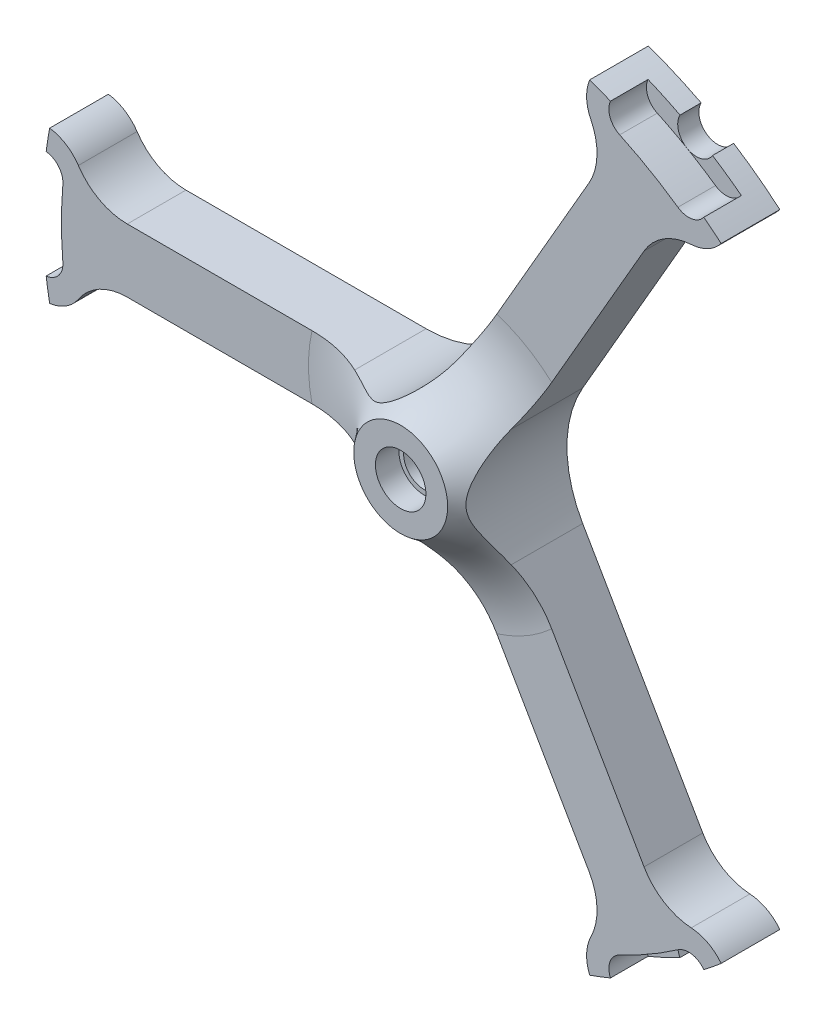
SolidWorks part; units mm, degrees
ref_plane "Plan de face" through (0, 0, 0) normal (0, 0, 1) x (1, 0, 0)
ref_plane "Plan de dessus" through (0, 0, 0) normal (0, 1, 0) x (1, 0, 0)
ref_plane "Plan de droite" through (0, 0, 0) normal (1, 0, 0) x (0, 0, -1)
sketch "Esquisse1" plane through (0, 0, 0) normal (0, 0, 1) x (1, 0, 0)
  line L19 (-1000, 0) -> (49000, 0) construction
  line L21 (-27.7888, 2.7) -> (-7.3323, 2.7)
  line L23 (-27.7888, -2.7) -> (-7.3323, -2.7)
  line L33 (16.2327, 22.7158) -> (6.0044, 5)
  line L34 (11.5561, 25.4158) -> (1.3279, 7.7)
  line L35 (11.5561, -25.4158) -> (1.3279, -7.7)
  line L36 (16.2327, -22.7158) -> (6.0044, -5)
  arc A0 (-34.3972, 6.4678) -> (-34.6976, 4.5906) centre (0, 0) ccw
  arc A7 (-33.2771, 2.8629) -> (-34.6976, 4.5906) centre (-34.8712, 3) ccw
  arc A8 (-33.2771, -2.8629) -> (-34.6976, -4.5906) centre (-34.8712, -3) cw
  arc A12 (-33.2771, 2.8629) -> (-33.2771, -2.8629) centre (0, 0) ccw
  arc A13 (-31.9549, 4.9353) -> (-34.3972, 6.4678) centre (-34.8712, 3) ccw
  arc A14 (-31.9549, -4.9353) -> (-34.3972, -6.4678) centre (-34.8712, -3) cw
  arc A15 (-34.6976, -4.5906) -> (-34.3972, -6.4678) centre (0, 0) ccw
  arc A16 (-27.7888, -2.7) -> (-31.9549, -4.9353) centre (-27.7888, -7.7) ccw
  arc A17 (-27.7888, 2.7) -> (-31.9549, 4.9353) centre (-27.7888, 7.7) cw
  arc A48 (22.7998, 26.555) -> (21.3244, 27.7538) centre (0, 0) ccw
  arc A49 (19.1178, 27.3874) -> (21.3244, 27.7538) centre (20.0337, 28.6993) ccw
  arc A50 (14.1592, 30.2502) -> (13.3733, 32.3443) centre (14.8375, 31.6993) cw
  arc A51 (19.1178, 27.3874) -> (14.1592, 30.2502) centre (0, 0) ccw
  arc A52 (20.2516, 25.2061) -> (22.7998, 26.555) centre (20.0337, 28.6993) ccw
  arc A53 (11.7034, 30.1414) -> (11.5974, 33.0227) centre (14.8375, 31.6993) cw
  arc A54 (13.3733, 32.3443) -> (11.5974, 33.0227) centre (0, 0) ccw
  arc A55 (11.5561, 25.4158) -> (11.7034, 30.1414) centre (7.226, 27.9158) ccw
  arc A56 (16.2327, 22.7158) -> (20.2516, 25.2061) centre (20.5628, 20.2158) cw
  arc A57 (11.5974, -33.0227) -> (13.3733, -32.3443) centre (0, 0) ccw
  arc A58 (14.1592, -30.2502) -> (13.3733, -32.3443) centre (14.8375, -31.6993) ccw
  arc A59 (19.1178, -27.3874) -> (21.3244, -27.7538) centre (20.0337, -28.6993) cw
  arc A60 (14.1592, -30.2502) -> (19.1178, -27.3874) centre (0, 0) ccw
  arc A61 (11.7034, -30.1414) -> (11.5974, -33.0227) centre (14.8375, -31.6993) ccw
  arc A62 (20.2516, -25.2061) -> (22.7998, -26.555) centre (20.0337, -28.6993) cw
  arc A63 (21.3244, -27.7538) -> (22.7998, -26.555) centre (0, 0) ccw
  arc A64 (16.2327, -22.7158) -> (20.2516, -25.2061) centre (20.5628, -20.2158) ccw
  arc A65 (11.5561, -25.4158) -> (11.7034, -30.1414) centre (7.226, -27.9158) cw
  arc A66 (-7.3323, -2.7) -> (1.3279, -7.7) centre (-7.3323, -12.7) cw
  arc A67 (6.0044, -5) -> (6.0044, 5) centre (14.6647, 0) cw
  arc A68 (1.3279, 7.7) -> (-7.3323, 2.7) centre (-7.3323, 12.7) cw
  point P38 (0, 0)
  point P50 (3.1177, 0)
  point P55 (0, 0)
  point P56 (0, 0)
  point P80 (0, 0)
  dimension "D1" = 70
  dimension "D3" = 3
  dimension "D2" = 3.2
  dimension "D4" = 5
  dimension "D5" = 10
extrude "Boss.-Extru.1" add sketch "Esquisse1" along normal blind 5
sketch "Esquisse7" plane through (0, 0, 0) normal (0, 0, -1) x (-1, 0, 0)
  line L0 (-1000, 0) -> (49000, 0) construction
  arc A0 (34.6976, -4.5906) -> (34.6976, 4.5906) centre (0, 0) ccw
  arc A2 (33.2771, -2.8629) -> (33.2771, 2.8629) centre (0, 0) ccw
  arc A4 (34.9634, 1.5996) -> (34.9634, -1.5996) centre (35, 0) ccw
  arc A5 (34.6976, 4.5906) -> (33.2771, 2.8629) centre (34.8712, 3) ccw
  arc A6 (33.2771, -2.8629) -> (33.2771, 2.8629) centre (0, 0) ccw construction
  arc A7 (34.6976, -4.5906) -> (33.2771, -2.8629) centre (34.8712, -3) cw
  arc A8 (-21.3244, -27.7538) -> (-13.3733, -32.3443) centre (0, 0) ccw
  arc A9 (-19.1178, -27.3874) -> (-14.1592, -30.2502) centre (0, 0) ccw
  arc A10 (-16.0964, -31.079) -> (-18.867, -29.4794) centre (-17.5, -30.3109) ccw
  arc A11 (-13.3733, -32.3443) -> (-14.1592, -30.2502) centre (-14.8375, -31.6993) ccw
  arc A12 (-21.3244, -27.7538) -> (-19.1178, -27.3874) centre (-20.0337, -28.6993) cw
  arc A13 (-13.3733, 32.3443) -> (-21.3244, 27.7538) centre (0, 0) ccw
  arc A14 (-14.1592, 30.2502) -> (-19.1178, 27.3874) centre (0, 0) ccw
  arc A15 (-18.867, 29.4794) -> (-16.0964, 31.079) centre (-17.5, 30.3109) ccw
  arc A16 (-21.3244, 27.7538) -> (-19.1178, 27.3874) centre (-20.0337, 28.6993) ccw
  arc A17 (-13.3733, 32.3443) -> (-14.1592, 30.2502) centre (-14.8375, 31.6993) cw
  point P36 (0, 0)
  arc M44 (34.6976, -4.5906) -> (33.2771, -2.8629) centre (34.8712, -3) cw
  arc M45 (33.2771, -2.8629) -> (33.2771, 2.8629) centre (0, 0) ccw
  arc M46 (33.2771, 2.8629) -> (34.6976, 4.5906) centre (34.8712, 3) cw
  arc M56 (-13.3733, 32.3443) -> (-14.1592, 30.2502) centre (-14.8375, 31.6993) cw
  arc M57 (-14.1592, 30.2502) -> (-19.1178, 27.3874) centre (0, 0) ccw
  arc M58 (-19.1178, 27.3874) -> (-21.3244, 27.7538) centre (-20.0337, 28.6993) cw
  arc M68 (-21.3244, -27.7538) -> (-19.1178, -27.3874) centre (-20.0337, -28.6993) cw
  arc M69 (-19.1178, -27.3874) -> (-14.1592, -30.2502) centre (0, 0) ccw
  arc M70 (-14.1592, -30.2502) -> (-13.3733, -32.3443) centre (-14.8375, -31.6993) cw
  dimension "D1" = 3.2
  dimension "D3" = 3.2
  dimension "D4" = 70
  dimension "D2" = 3
extrude "Boss.-Extru.5" add sketch "Esquisse7" against normal blind 1.8 contours A4 A0 A2 M46 | A4 A0 M45 M44 | A10 A8 A9 M70 | A10 A8 M69 M68 | A15 A13 M57 M56 | A15 A13 A14 M58 region at (-34.0862, -2.7129, 0) region at (-34.0862, 2.7129, 0) region at (19.3926, -28.1631, 0) region at (14.6937, -30.876, 0) region at (14.6937, 30.876, 0) region at (19.3926, 28.1631, 0)
sketch "Esquisse4" plane through (0, 0, 5) normal (0, 0, 1) x (1, 0, 0)
  circle A1 centre (0, 0) radius 4
  dimension "D1" = 8
extrude "Boss.-Extru.3" add sketch "Esquisse4" along normal blind 4.5
sketch "Esquisse5" plane through (0, 0, 9.5) normal (0, 0, 1) x (1, 0, 0)
  circle A0 centre (0, 0) radius 2.15
  dimension "D1" = 4.3
extrude "Enlèv. mat.-Extru.2" cut sketch "Esquisse5" against normal blind 2
fillet "Congé1" radius 10 1 edges at (4, 0, 5)
sketch "Esquisse6" plane through (0, 0, 7.5) normal (0, 0, 1) x (1, 0, 0)
  circle A0 centre (0, 0) radius 1.75
  dimension "D1" = 3.5
extrude "Enlèv. mat.-Extru.3" cut sketch "Esquisse6" against normal up to next
